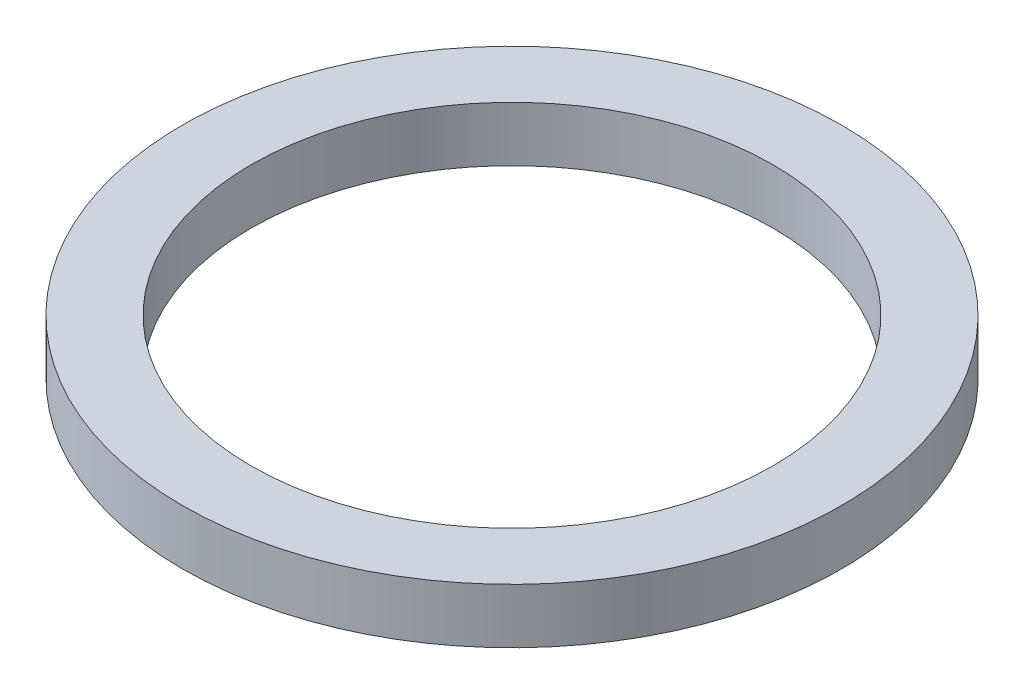
SolidWorks part; units mm, degrees
ref_plane "Front Plane" through (0, 0, 0) normal (0, 0, 1) x (1, 0, 0)
ref_plane "Top Plane" through (0, 0, 0) normal (0, 1, 0) x (1, 0, 0)
ref_plane "Right Plane" through (0, 0, 0) normal (1, 0, 0) x (0, 0, -1)
sketch "Sketch1" plane through (0, 0, 0) normal (0, 1, 0) x (1, 0, 0)
  circle A0 centre (0, 0) radius 47.5
  circle A1 centre (0, 0) radius 60
  dimension "D1" = 95
  dimension "D2" = 120
extrude "Boss-Extrude1" add sketch "Sketch1" along normal blind 10
